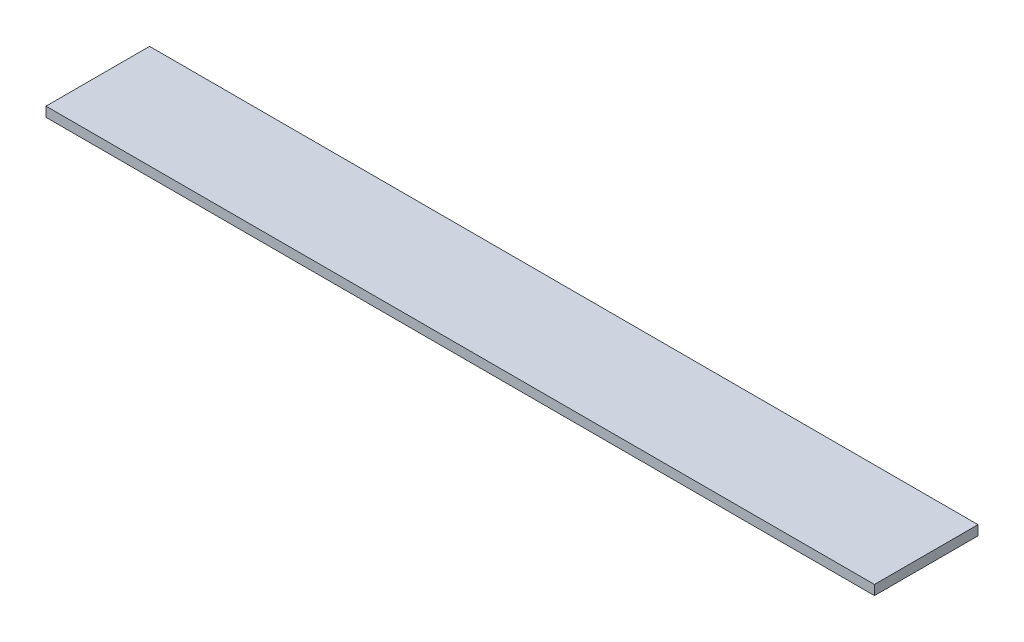
SolidWorks part; units mm, degrees
ref_plane "Front Plane" through (0, 0, 0) normal (0, 0, 1) x (1, 0, 0)
ref_plane "Top Plane" through (0, 0, 0) normal (0, 1, 0) x (1, 0, 0)
ref_plane "Right Plane" through (0, 0, 0) normal (1, 0, 0) x (0, 0, -1)
sketch "Sketch1" plane through (0, 0, 0) normal (0, 1, 0) x (1, 0, 0)
  line L1 (0, 0) -> (406.4, 0)
  line L2 (0, 0) -> (0, 50.8)
  line L3 (0, 50.8) -> (406.4, 50.8)
  line L4 (406.4, 0) -> (406.4, 50.8)
  dimension "D1" = 406.4
  dimension "D2" = 50.8
extrude "Boss-Extrude1" add sketch "Sketch1" along normal blind 4.7625
